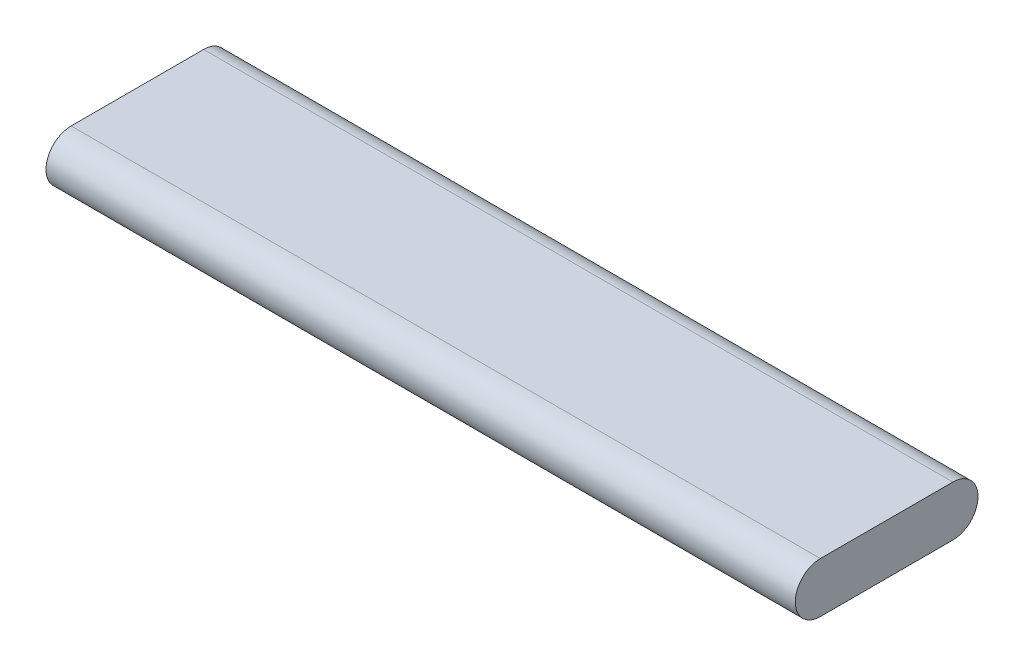
SolidWorks part; units mm, degrees
ref_plane "前视基准面" through (0, 0, 0) normal (0, 0, 1) x (1, 0, 0)
ref_plane "上视基准面" through (0, 0, 0) normal (0, 1, 0) x (1, 0, 0)
ref_plane "右视基准面" through (0, 0, 0) normal (1, 0, 0) x (0, 0, -1)
sketch "草图1" plane through (0, 0, 0) normal (0, 1, 0) x (1, 0, 0)
  line L1 (0, 0) -> (82, 0)
  line L2 (0, 0) -> (0, -20)
  line L3 (0, -20) -> (82, -20)
  line L4 (82, 0) -> (82, -20)
  dimension "D1" = 82
  dimension "D2" = 20
extrude "凸台-拉伸1" add sketch "草图1" along normal blind 5.5
fillet "圆角1" 2 edges at (41, 5.5, 0) (41, 0, 0) type full round first side face at (41, 5.5, 10) second side face at (41, 0, 10) middle face at (41, 2.75, 0)
fillet "圆角2" 2 edges at (41, 5.5, 20) (41, 0, 20) type full round first side face at (41, 5.5, 11.375) second side face at (41, 0, 11.375) middle face at (41, 2.75, 20)
